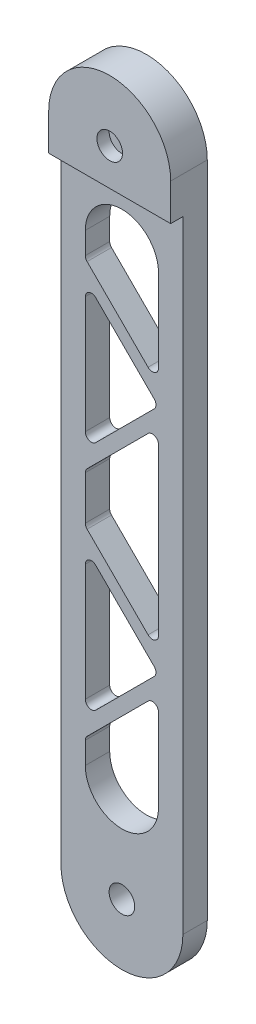
SolidWorks part; units mm, degrees
material "PLA"
ref_plane "Alzado" through (0, 0, 0) normal (0, 0, 1) x (1, 0, 0)
ref_plane "Planta" through (0, 0, 0) normal (0, 1, 0) x (1, 0, 0)
ref_plane "Vista lateral" through (0, 0, 0) normal (1, 0, 0) x (0, 0, -1)
sketch "Croquis1" plane through (0, 0, 0) normal (0, 0, 1) x (1, 0, 0)
  line L0 (0, 54) -> (0, -54) construction
  line L1 (10, 54) -> (10, -54)
  line L2 (-10, 54) -> (-10, -54)
  line L3 (0, 38) -> (0, -38) construction
  line L4 (6, 38) -> (6, -38)
  line L5 (-6, 38) -> (-6, -38)
  line L6 (-10, -47.95) -> (10, -47.95)
  line L7 (0, 51.9) -> (0, 44) construction
  line L8 (-10, 47.95) -> (10, 47.95)
  line L9 (0, -51.9) -> (0, -44) construction
  line L10 (0, 0) -> (0, -38) construction
  line L11 (-6, 0) -> (6, 0) construction
  line L12 (-6, -34) -> (6, -22)
  line L13 (-6, -31) -> (6, -19)
  line L14 (-6, -19) -> (6, -19) construction
  line L16 (-6, -7) -> (6, -19)
  line L17 (-6, -4) -> (6, -16)
  line L18 (-6, 4) -> (6, 16)
  line L19 (-6, 7) -> (6, 19)
  line L20 (-6, 31) -> (6, 19)
  line L21 (-6, 34) -> (6, 22)
  arc A0 (10, 54) -> (-10, 54) centre (0, 54) ccw
  arc A1 (-10, -54) -> (10, -54) centre (0, -54) ccw
  circle A2 centre (0, 54) radius 2.1
  circle A3 centre (0, -54) radius 2.1
  arc A4 (6, 38) -> (-6, 38) centre (0, 38) ccw
  arc A5 (-6, -38) -> (6, -38) centre (0, -38) ccw
  point P2 (0, 0)
  point P14 (0, 0)
  point P23 (0, 47.95)
  point P28 (0, -47.95)
  point P37 (0, -19)
  point P50 (6, -19)
  dimension "D1" = 4.2
  dimension "D2" = 20
  dimension "D3" = 108
  dimension "D4" = 4
  dimension "D5" = 16
  dimension "D6" = 135
  dimension "D7" = 3
extrude "Saliente-Extruir1" add sketch "Croquis1" along normal blind 4 contours L2 A1 L1 L8 A5 L5 A4 L4 A3 | L13 L5 L12 L4 | L17 L5 L16 L4 | L19 L5 L18 L4 | L21 L5 L20 L4 | L2 A1 L1 A0 | A3 | L5 A5 L4 A4 region at (9.0204, 0, 0) region at (0, 26.5, 0) region at (0, 11.5, 0) region at (0, -11.5, 0) region at (0, -26.5, 0)
extrude "Saliente-Extruir3" add sketch "Croquis1<6>" along normal blind 6 contours L1 A0 L2 L8 A2 region at (9.7436, 50.975, 0)
sketch "Croquis1<6>" plane through (0, 0, 0) normal (0, 0, 1) x (1, 0, 0) same geometry as "Croquis1"
fillet "Redondeo1" radius 1 14 edges at (6, 22, 2) (6, 16, 2) (6, 19, 2) (-6, 31, 2) (-6, 7, 2) (6, -22, 2) (6, -16, 2) (6, -19, 2) (-6, -31, 2) (-6, -7, 2) (-6, 34, 2) (-6, -4, 2) (-6, -34, 2) (-6, 4, 2)
